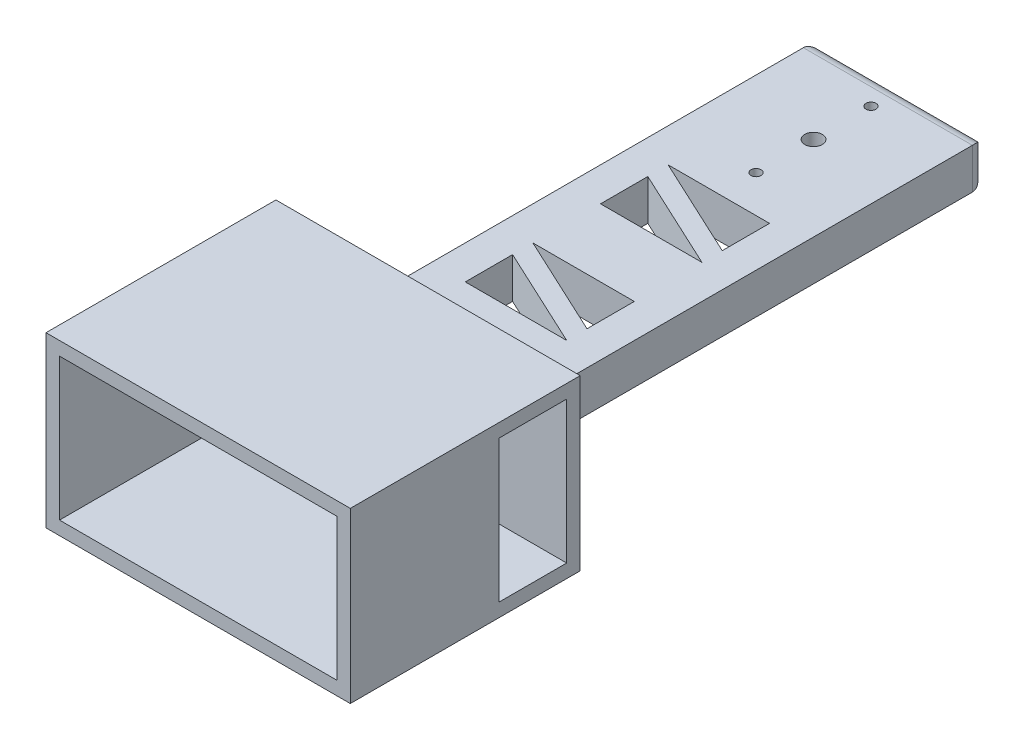
SolidWorks part; units mm, degrees
ref_plane "Front Plane" through (0, 0, 0) normal (0, 0, 1) x (1, 0, 0)
ref_plane "Top Plane" through (0, 0, 0) normal (0, 1, 0) x (1, 0, 0)
ref_plane "Right Plane" through (0, 0, 0) normal (1, 0, 0) x (0, 0, -1)
sketch "Sketch1" plane through (0, 0, 0) normal (0, 0, 1) x (1, 0, 0)
  line L1 (-12.5, -3) -> (12.5, -3)
  line L2 (-12.5, -3) -> (-12.5, 3)
  line L3 (-12.5, 3) -> (12.5, 3)
  line L4 (12.5, -3) -> (12.5, 3)
  line L5 (-12.5, -3) -> (12.5, 3) construction
  line L6 (-12.5, 3) -> (12.5, -3) construction
  point P0 (0, 0)
  dimension "D1" = 25
  dimension "D2" = 6
extrude "Boss-Extrude1" add sketch "Sketch1" along normal blind 70
fillet "Fillet1" radius 2 4 edges at (12.5, 0, 0) (-12.5, 0, 0) (0, 3, 0) (0, -3, 0)
sketch "Sketch2" plane through (0, 3, 0) normal (0, 1, 0) x (1, 0, 0)
  line L0 (12.5, -70) -> (12.5, -2) construction
  line L1 (7.5, -7) -> (-7.5, -7)
  line L2 (7.5, -7) -> (7.5, -65)
  line L3 (7.5, -65) -> (-7.5, -65)
  line L4 (-7.5, -7) -> (-7.5, -65)
  line L5 (-12.5, -70) -> (-12.5, -2) construction
  line L6 (12.5, -2) -> (-12.5, -2) construction
  line L7 (12.5, -70) -> (-12.5, -70) construction
  line L8 (-7.5, -7) -> (7.5, -13.9946)
  line L9 (7.5, -16.9946) -> (-7.5, -10)
  line L10 (7.5, -16.9946) -> (-7.5, -16.9946)
  dimension "D1" = 5
  dimension "D2" = 5
  dimension "D3" = 5
  dimension "D4" = 5
  dimension "D5" = 25
  dimension "D6" = 3
extrude "Cut-Extrude1" cut sketch "Sketch2" against normal up to next contours L10 L9 L4 | L1 L8 L2 region at (2.5, 3, 9.3315) region at (-2.5, 3, 14.6631)
pattern_linear "LPattern1" count 3 spacing 20 along (0, 0, 1) of "Cut-Extrude1"
sketch "Sketch3" plane through (0, 3, 0) normal (0, 1, 0) x (1, 0, 0)
  line L1 (-7.5, -7) -> (7.5, -7)
  line L2 (-7.5, -7) -> (-7.5, -16.9946)
  line L3 (-7.5, -16.9946) -> (7.5, -16.9946)
  line L4 (7.5, -7) -> (7.5, -16.9946)
extrude "Boss-Extrude4" add sketch "Sketch3" against normal up to surface (6 mm away) contours L2 L1 L4 L3 up to face at (2.5, -3, 49.3315)
sketch "Sketch4" plane through (0, 0, 70) normal (0, 0, 1) x (1, 0, 0)
  line L6 (-22.5, -12.5) -> (22.5, -12.5)
  line L10 (-22.5, -12.5) -> (-22.5, 12.5)
  line L11 (-22.5, 12.5) -> (22.5, 12.5)
  line L12 (22.5, -12.5) -> (22.5, 12.5)
  line L13 (-22.5, -12.5) -> (22.5, 12.5) construction
  line L14 (-22.5, 12.5) -> (22.5, -12.5) construction
  point P0 (0, 0)
  point P1 (0, 0)
  dimension "D1" = 45
  dimension "D2" = 25
extrude "Boss-Extrude5" add sketch "Sketch4" along normal blind 2
sketch "Sketch5" plane through (0, 0, 72) normal (0, 0, 1) x (1, 0, 0)
  line L8 (20.5, -10.5) -> (20.5, 10.5)
  line L9 (20.5, 10.5) -> (-20.5, 10.5)
  line L10 (-20.5, 10.5) -> (-20.5, -10.5)
  line L11 (-20.5, -10.5) -> (20.5, -10.5)
  line L12 (20.5, -10.5) -> (20.5, 10.5)
  line L13 (20.5, 10.5) -> (-20.5, 10.5)
  line L14 (-20.5, 10.5) -> (-20.5, -10.5)
  line L15 (-20.5, -10.5) -> (20.5, -10.5)
  line L16 (22.5, -12.5) -> (22.5, 12.5)
  line L17 (22.5, 12.5) -> (-22.5, 12.5)
  line L18 (-22.5, 12.5) -> (-22.5, -12.5)
  line L19 (-22.5, -12.5) -> (22.5, -12.5)
  line L20 (22.5, -12.5) -> (22.5, 12.5)
  line L21 (22.5, 12.5) -> (-22.5, 12.5)
  line L22 (-22.5, 12.5) -> (-22.5, -12.5)
  line L23 (-22.5, -12.5) -> (22.5, -12.5)
  dimension "D1" = 2
  dimension "D2" = 0
extrude "Boss-Extrude6" add sketch "Sketch5" along normal blind 32
fillet "Fillet2" radius 5 4 edges at (0, 3, 70) (-12.5, 0, 70) (12.5, 0, 70) (0, -3, 70)
sketch "Sketch6" plane through (0, 0, 104) normal (0, 0, 1) x (1, 0, 0)
  line L0 (22.5, 12.5) -> (-22.5, 12.5) construction
  line L1 (-28.5, -12.5) -> (28.5, -12.5)
  line L2 (-28.5, -12.5) -> (-28.5, 12.5)
  line L3 (-28.5, 12.5) -> (28.5, 12.5)
  line L4 (28.5, -12.5) -> (28.5, 12.5)
  line L5 (-28.5, -12.5) -> (28.5, 12.5) construction
  line L6 (-28.5, 12.5) -> (28.5, -12.5) construction
  line L7 (0, 27.5306) -> (0, -27.9773) construction
  line L8 (42.5341, 0) -> (-46.7994, 0) construction
  line L9 (20.5, -10.5) -> (20.5, 10.5) construction
  line L10 (22.5, -12.5) -> (22.5, 12.5) construction
  circle A0 centre (24, 5) radius 1.3
  point P0 (0, 0)
  dimension "D1" = 2.6
  dimension "D2" = 3.5
  dimension "D3" = 5
  dimension "D4" = 6
sketch "Sketch8" plane through (22.5, 0, 0) normal (1, 0, 0) x (0, 0, -1)
  line L0 (-104, 12.5) -> (-70, 12.5) construction
  line L1 (-82, 10.5) -> (-72, 10.5)
  line L2 (-82, 10.5) -> (-82, -10.5)
  line L3 (-82, -10.5) -> (-72, -10.5)
  line L4 (-72, 10.5) -> (-72, -10.5)
  line L5 (-104, -12.5) -> (-70, -12.5) construction
  line L7 (-70, -12.5) -> (-70, 12.5) construction
  dimension "D1" = 2
  dimension "D2" = 2
  dimension "D3" = 2
  dimension "D4" = 10
extrude "Cut-Extrude2" cut sketch "Sketch8" against normal up to surface (45 mm away) up to face at (-22.5, 0, 87)
sketch "Sketch9" plane through (0, -3, 0) normal (0, -1, 0) x (1, 0, 0)
  line L0 (-16.0531, 13) -> (16.0819, 13) construction
  circle A0 centre (0, 13) radius 10.5
  circle A1 centre (0, 13) radius 1.3
  circle A2 centre (0, 21.5) radius 0.75
  circle A3 centre (0, 4.5) radius 0.75
  point P10 (0, 0)
  dimension "D2" = 21
  dimension "D3" = 2.6
  dimension "D4" = 1.5
  dimension "D1" = 13
  dimension "D5" = 8.5
extrude "Cut-Extrude3" cut sketch "Sketch9" against normal up to next contours L0 A1 | A1 L0 | A2 | A3 | A1 region at (0, -3, 12.4483) region at (0, -3, 13.5517) region at (0, -3, 21.5) region at (0, -3, 4.5)
